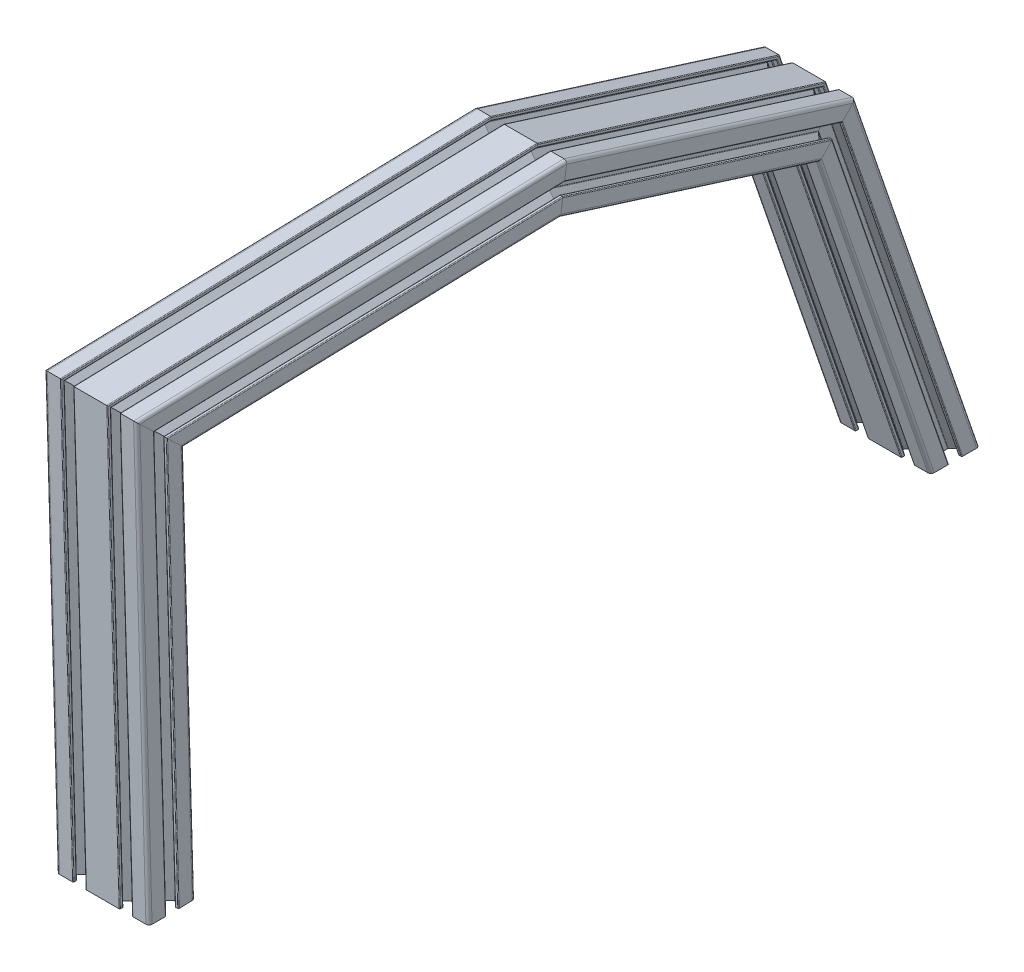
SolidWorks part; units mm, degrees
ref_plane "Front Plane" through (0, 0, 0) normal (0, 0, 1) x (1, 0, 0)
ref_plane "Top Plane" through (0, 0, 0) normal (0, 1, 0) x (1, 0, 0)
ref_plane "Right Plane" through (0, 0, 0) normal (1, 0, 0) x (0, 0, -1)
sketch "Sketch2" plane through (66.7101, 0, 48.5855) normal (0, 1, 0) x (1, 0, 0)
  line L1 (-190.5, -254) -> (190.5, -254)
  line L2 (-190.5, -254) -> (-190.5, 254)
  line L3 (-190.5, 254) -> (190.5, 254)
  line L4 (190.5, -254) -> (190.5, 254)
  line L5 (-190.5, -254) -> (190.5, 254) construction
  line L6 (-190.5, 254) -> (190.5, -254) construction
  point P0 (0, 0)
sketch "Sketch3" plane through (0, 0, 0) normal (0, 1, 0) x (1, 0, 0)
  line L0 (66.7101, -48.5855) -> (66.7101, -302.5855) construction
  line L1 (66.7101, -302.5855) -> (66.7101, 205.4145) construction
  line L2 (-123.7899, -302.5855) -> (257.2101, -302.5855) construction
  line L10 (-123.7899, 205.4145) -> (257.2101, 205.4145) construction
ref_plane "Plane1" through (66.7101, 0, 0) normal (1, 0, 0) x (0, 0, -1)
sketch "Sketch5" plane through (66.7101, 0, 0) normal (1, 0, 0) x (0, 0, -1)
  line L0 (-48.5855, 0) -> (-48.5855, 279.4) construction
  line L1 (-302.5855, 0) -> (-310.1662, 272.1127)
  line L2 (-302.5855, 0) -> (205.4145, 0) construction
  line L3 (-302.5855, 0) -> (205.4145, 0) construction
  line L4 (-310.1662, 272.1127) -> (-48.5855, 279.4)
  line L5 (-48.5855, 279.4) -> (128.7709, 223.4967)
  line L6 (128.7709, 223.4967) -> (217.8615, -36.2959)
  point P28 (217.8615, -36.2959)
  dimension "D1" = 279.4
other "8020 6030(1)" corner treatment miter
ref_plane "Plane2" through (66.7101, 0, 302.5855) normal (0, -0.9996, -0.0278) x (1, 0, 0)
sketch "Sketch21" plane through (66.7101, 0, 302.5855) normal (0, -0.9996, -0.0278) x (1, 0, 0)
  line L0 (11.1749, 2.3185) -> (11.9567, 1.3394) construction
  line L1 (13.6606, 3.0433) -> (12.6815, 3.8251) construction
  line L2 (-4.55, 12.3) -> (-4.55, 9.2682)
  line L3 (4.05, 12.8) -> (-4.05, 12.8)
  line L4 (4.55, 9.2682) -> (4.55, 12.3)
  line L5 (9.0188, 4.178) -> (4.9893, 8.2075)
  line L6 (9.1653, 0.8875) -> (9.1653, 3.8245)
  line L7 (9.6753, -0.0625) -> (9.1653, 0.8875) construction
  line L8 (9.1653, -1.0125) -> (9.6753, -0.0625) construction
  line L9 (9.1653, -3.8245) -> (9.1653, -1.0125)
  line L10 (4.9893, -8.2075) -> (9.0188, -4.178)
  line L11 (4.55, -12.3) -> (4.55, -9.2682)
  line L12 (-4.05, -12.8) -> (4.05, -12.8)
  line L13 (-4.55, -9.2682) -> (-4.55, -12.3)
  line L14 (-9.0188, -4.178) -> (-4.9893, -8.2075)
  line L15 (-9.1653, -1.0125) -> (-9.1653, -3.8245)
  line L16 (-9.6753, -0.0625) -> (-9.1653, -1.0125) construction
  line L17 (-9.1653, 0.8875) -> (-9.6753, -0.0625) construction
  line L18 (-9.1653, 3.8245) -> (-9.1653, 0.8875)
  line L19 (-4.9893, 8.2075) -> (-9.0188, 4.178)
  line L20 (17.3185, 3.8251) -> (16.3393, 3.0433) construction
  line L21 (18.0433, 1.3394) -> (18.8251, 2.3185) construction
  line L22 (18.8251, -2.3185) -> (18.0433, -1.3394) construction
  line L23 (16.3393, -3.0433) -> (17.3185, -3.8251) construction
  line L24 (12.6856, -3.8343) -> (13.6707, -3.0477) construction
  line L25 (11.9608, -1.3486) -> (11.179, -2.3278) construction
  line L26 (-18.8251, 2.3185) -> (-18.0433, 1.3394) construction
  line L27 (-16.3393, 3.0433) -> (-17.3185, 3.8251) construction
  line L28 (-12.6815, 3.8251) -> (-13.6606, 3.0433) construction
  line L29 (-11.9567, 1.3394) -> (-11.1749, 2.3185) construction
  line L30 (-11.1749, -2.3185) -> (-11.9567, -1.3394) construction
  line L31 (-13.6606, -3.0433) -> (-12.6815, -3.8251) construction
  line L32 (-17.3144, -3.8343) -> (-16.3292, -3.0477) construction
  line L33 (-18.0392, -1.3486) -> (-18.821, -2.3278) construction
  line L34 (-24.5, 9.88) -> (-24.5, 13.319)
  line L35 (-28.3189, 9.5) -> (-24.88, 9.5)
  line L36 (-28.6999, 12.7) -> (-28.6999, 9.881)
  line L37 (-24.881, 13.7) -> (-27.6999, 13.7)
  line L38 (-7.2674, -12.7425) -> (-10.4375, -12.7425)
  line L39 (-10.9375, -13.2425) -> (-10.9375, -14.5)
  line L40 (-10.4375, -15) -> (10.4375, -15)
  line L41 (10.9375, -14.5) -> (10.9375, -13.2425)
  line L42 (10.4375, -12.7425) -> (7.2674, -12.7425)
  line L43 (6.75, -12.2428) -> (6.75, -10.2602)
  line L44 (6.8964, -9.9067) -> (10.822, -5.9811)
  line L45 (11.1755, -5.8347) -> (14.05, -5.8347)
  line L46 (14.05, -5.8347) -> (15, -5.3247) construction
  line L47 (15, -5.3247) -> (15.95, -5.8347) construction
  line L48 (15.95, -5.8347) -> (18.8244, -5.8347)
  line L49 (19.178, -5.9811) -> (23.1035, -9.9067)
  line L50 (23.25, -10.2602) -> (23.25, -12.2428)
  line L51 (22.7325, -12.7425) -> (19.4375, -12.7425)
  line L52 (18.9375, -13.2425) -> (18.9375, -14.5)
  line L53 (19.4375, -15) -> (27.9999, -15)
  line L54 (29.9999, -13) -> (29.9999, -4.5625)
  line L55 (29.4999, -4.0625) -> (28.2425, -4.0625)
  line L56 (27.7425, -4.5625) -> (27.7425, -7.7325)
  line L57 (27.2428, -8.25) -> (25.2602, -8.25)
  line L58 (24.9066, -8.1035) -> (20.9811, -4.178)
  line L59 (20.8347, -3.8245) -> (20.8347, -1.0125)
  line L60 (20.8347, -1.0125) -> (20.3247, -0.0625) construction
  line L61 (20.3247, -0.0625) -> (20.8347, 0.8875) construction
  line L62 (20.8347, 0.8875) -> (20.8347, 3.8245)
  line L63 (20.9811, 4.178) -> (24.9066, 8.1035)
  line L64 (25.2602, 8.25) -> (27.2428, 8.25)
  line L65 (27.7425, 7.7325) -> (27.7425, 4.4375)
  line L66 (28.2425, 3.9375) -> (29.4999, 3.9375)
  line L67 (29.9999, 4.4375) -> (29.9999, 13)
  line L68 (27.9999, 15) -> (19.5625, 15)
  line L69 (19.0625, 14.5) -> (19.0625, 13.2425)
  line L70 (19.5625, 12.7425) -> (22.7325, 12.7425)
  line L71 (23.25, 12.2428) -> (23.25, 10.2602)
  line L72 (23.1035, 9.9067) -> (19.178, 5.9811)
  line L73 (18.8244, 5.8347) -> (15.95, 5.8347)
  line L74 (15.95, 5.8347) -> (15, 5.3247) construction
  line L75 (15, 5.3247) -> (14.05, 5.8347) construction
  line L76 (14.05, 5.8347) -> (11.1755, 5.8347)
  line L77 (10.822, 5.9811) -> (6.8964, 9.9067)
  line L78 (6.75, 10.2602) -> (6.75, 12.2428)
  line L79 (7.2674, 12.7425) -> (10.5625, 12.7425)
  line L80 (11.0625, 13.2425) -> (11.0625, 14.5)
  line L81 (10.5625, 15) -> (-10.5625, 15)
  line L82 (-11.0625, 14.5) -> (-11.0625, 13.2425)
  line L83 (-10.5625, 12.7425) -> (-7.2674, 12.7425)
  line L84 (-6.75, 12.2428) -> (-6.75, 10.2602)
  line L85 (-6.8964, 9.9067) -> (-10.822, 5.9811)
  line L86 (-11.1755, 5.8347) -> (-14.05, 5.8347)
  line L87 (-14.05, 5.8347) -> (-15, 5.3247) construction
  line L88 (-15, 5.3247) -> (-15.95, 5.8347) construction
  line L89 (-15.95, 5.8347) -> (-18.8244, 5.8347)
  line L90 (-19.178, 5.9811) -> (-23.1035, 9.9067)
  line L91 (-23.25, 10.2602) -> (-23.25, 12.2428)
  line L92 (-22.7325, 12.7425) -> (-19.5625, 12.7425)
  line L93 (-19.0625, 13.2425) -> (-19.0625, 14.5)
  line L94 (-19.5625, 15) -> (-27.9999, 15)
  line L95 (-29.9999, 13) -> (-29.9999, 4.4375)
  line L96 (-29.4999, 3.9375) -> (-28.2425, 3.9375)
  line L97 (-27.7425, 4.4375) -> (-27.7425, 7.7325)
  line L98 (-27.2428, 8.25) -> (-25.2602, 8.25)
  line L99 (-24.9066, 8.1035) -> (-20.9811, 4.178)
  line L100 (-20.8347, 3.8245) -> (-20.8347, 0.8875)
  line L101 (-20.8347, 0.8875) -> (-20.3247, -0.0625) construction
  line L102 (-20.3247, -0.0625) -> (-20.8347, -1.0125) construction
  line L103 (-20.8347, -1.0125) -> (-20.8347, -3.8245)
  line L104 (-20.9811, -4.178) -> (-24.9066, -8.1035)
  line L105 (-25.2602, -8.25) -> (-27.2428, -8.25)
  line L106 (-27.7425, -7.7325) -> (-27.7425, -4.5625)
  line L107 (-28.2425, -4.0625) -> (-29.4999, -4.0625)
  line L108 (-29.9999, -4.5625) -> (-29.9999, -13)
  line L109 (-27.9999, -15) -> (-19.4375, -15)
  line L110 (-18.9375, -14.5) -> (-18.9375, -13.2425)
  line L111 (-19.4375, -12.7425) -> (-22.7325, -12.7425)
  line L112 (-23.25, -12.2428) -> (-23.25, -10.2602)
  line L113 (-23.1035, -9.9067) -> (-19.178, -5.9811)
  line L114 (-18.8244, -5.8347) -> (-15.95, -5.8347)
  line L115 (-15.95, -5.8347) -> (-15, -5.3247) construction
  line L116 (-15, -5.3247) -> (-14.05, -5.8347) construction
  line L117 (-14.05, -5.8347) -> (-11.1755, -5.8347)
  line L118 (-10.822, -5.9811) -> (-6.8964, -9.9067)
  line L119 (-6.75, -10.2602) -> (-6.75, -12.2428)
  line L120 (-24.88, -9.5) -> (-28.3189, -9.5)
  line L121 (-24.5, -13.319) -> (-24.5, -9.88)
  line L122 (-27.6999, -13.7) -> (-24.881, -13.7)
  line L123 (-28.6999, -9.881) -> (-28.6999, -12.7)
  line L124 (24.5, -9.88) -> (24.5, -13.319)
  line L125 (28.3189, -9.5) -> (24.88, -9.5)
  line L126 (28.6999, -12.7) -> (28.6999, -9.881)
  line L127 (24.881, -13.7) -> (27.6999, -13.7)
  line L128 (27.6999, 13.7) -> (24.881, 13.7)
  line L129 (28.6999, 9.881) -> (28.6999, 12.7)
  line L130 (24.88, 9.5) -> (28.3189, 9.5)
  line L131 (24.5, 13.319) -> (24.5, 9.88)
  line L132 (-14.05, 5.8347) -> (-15.95, 5.8347)
  line L133 (-20.8347, 0.8875) -> (-20.8347, -1.0125)
  line L134 (-15.95, -5.8347) -> (-14.05, -5.8347)
  line L135 (-9.1653, -1.0125) -> (-9.1653, 0.8875)
  line L136 (9.1653, 0.8875) -> (9.1653, -1.0125)
  line L137 (14.05, -5.8347) -> (15.95, -5.8347)
  line L138 (20.8347, -1.0125) -> (20.8347, 0.8875)
  line L139 (15.95, 5.8347) -> (14.05, 5.8347)
  arc A0 (-4.05, 12.8) -> (-4.55, 12.3) centre (-4.05, 12.3) ccw
  arc A1 (4.55, 12.3) -> (4.05, 12.8) centre (4.05, 12.3) ccw
  arc A2 (4.55, 9.2682) -> (4.9893, 8.2075) centre (6.05, 9.2682) ccw
  arc A3 (9.1653, 3.8245) -> (9.0188, 4.178) centre (8.6653, 3.8245) ccw
  arc A4 (9.0188, -4.178) -> (9.1653, -3.8245) centre (8.6653, -3.8245) ccw
  arc A5 (4.9893, -8.2075) -> (4.55, -9.2682) centre (6.05, -9.2682) ccw
  arc A6 (4.05, -12.8) -> (4.55, -12.3) centre (4.05, -12.3) ccw
  arc A7 (-4.55, -12.3) -> (-4.05, -12.8) centre (-4.05, -12.3) ccw
  arc A8 (-4.55, -9.2682) -> (-4.9893, -8.2075) centre (-6.05, -9.2682) ccw
  arc A9 (-9.1653, -3.8245) -> (-9.0188, -4.178) centre (-8.6653, -3.8245) ccw
  arc A10 (-9.0188, 4.178) -> (-9.1653, 3.8245) centre (-8.6653, 3.8245) ccw
  arc A11 (-4.9893, 8.2075) -> (-4.55, 9.2682) centre (-6.05, 9.2682) ccw
  arc A12 (12.6815, 3.8251) -> (11.1749, 2.3185) centre (12.0126, 2.9874) ccw construction
  arc A13 (16.3393, 3.0433) -> (13.6606, 3.0433) centre (15, 0) ccw construction
  arc A14 (18.8251, 2.3185) -> (17.3185, 3.8251) centre (17.9873, 2.9874) ccw construction
  arc A15 (18.0433, -1.3394) -> (18.0433, 1.3394) centre (15, 0) ccw construction
  arc A16 (17.3185, -3.8251) -> (18.8251, -2.3185) centre (17.9873, -2.9874) ccw construction
  arc A17 (13.6707, -3.0477) -> (16.3393, -3.0433) centre (15, 0) ccw construction
  arc A18 (11.179, -2.3278) -> (12.6856, -3.8343) centre (12.0167, -2.9966) ccw construction
  arc A19 (11.9567, 1.3394) -> (11.9608, -1.3486) centre (15, 0) ccw construction
  arc A20 (-17.3185, 3.8251) -> (-18.8251, 2.3185) centre (-17.9873, 2.9874) ccw construction
  arc A21 (-13.6606, 3.0433) -> (-16.3393, 3.0433) centre (-15, 0) ccw construction
  arc A22 (-11.1749, 2.3185) -> (-12.6815, 3.8251) centre (-12.0126, 2.9874) ccw construction
  arc A23 (-11.9567, -1.3394) -> (-11.9567, 1.3394) centre (-15, 0) ccw construction
  arc A24 (-12.6815, -3.8251) -> (-11.1749, -2.3185) centre (-12.0126, -2.9874) ccw construction
  arc A25 (-16.3292, -3.0477) -> (-13.6606, -3.0433) centre (-15, 0) ccw construction
  arc A26 (-18.821, -2.3278) -> (-17.3144, -3.8343) centre (-17.9833, -2.9966) ccw construction
  arc A27 (-18.0433, 1.3394) -> (-18.0392, -1.3486) centre (-15, 0) ccw construction
  arc A28 (-7.2674, -12.7425) -> (-6.75, -12.2428) centre (-7.25, -12.2428) ccw
  arc A29 (-10.4375, -12.7425) -> (-10.9375, -13.2425) centre (-10.4375, -13.2425) ccw
  arc A30 (-10.9375, -14.5) -> (-10.4375, -15) centre (-10.4375, -14.5) ccw
  arc A31 (10.4375, -15) -> (10.9375, -14.5) centre (10.4375, -14.5) ccw
  arc A32 (10.9375, -13.2425) -> (10.4375, -12.7425) centre (10.4375, -13.2425) ccw
  arc A33 (6.75, -12.2428) -> (7.2674, -12.7425) centre (7.25, -12.2428) ccw
  arc A34 (6.8964, -9.9067) -> (6.75, -10.2602) centre (7.25, -10.2602) ccw
  arc A35 (11.1755, -5.8347) -> (10.822, -5.9811) centre (11.1755, -6.3347) ccw
  arc A36 (19.178, -5.9811) -> (18.8244, -5.8347) centre (18.8244, -6.3347) ccw
  arc A37 (23.25, -10.2602) -> (23.1035, -9.9067) centre (22.75, -10.2602) ccw
  arc A38 (22.7325, -12.7425) -> (23.25, -12.2428) centre (22.75, -12.2428) ccw
  arc A39 (19.4375, -12.7425) -> (18.9375, -13.2425) centre (19.4375, -13.2425) ccw
  arc A40 (18.9375, -14.5) -> (19.4375, -15) centre (19.4375, -14.5) ccw
  arc A41 (27.9999, -15) -> (29.9999, -13) centre (27.9999, -13) ccw
  arc A42 (29.9999, -4.5625) -> (29.4999, -4.0625) centre (29.4999, -4.5625) ccw
  arc A43 (28.2425, -4.0625) -> (27.7425, -4.5625) centre (28.2425, -4.5625) ccw
  arc A44 (27.2428, -8.25) -> (27.7425, -7.7325) centre (27.2428, -7.75) ccw
  arc A45 (24.9066, -8.1035) -> (25.2602, -8.25) centre (25.2602, -7.75) ccw
  arc A46 (20.8347, -3.8245) -> (20.9811, -4.178) centre (21.3347, -3.8245) ccw
  arc A47 (20.9811, 4.178) -> (20.8347, 3.8245) centre (21.3347, 3.8245) ccw
  arc A48 (25.2602, 8.25) -> (24.9066, 8.1035) centre (25.2602, 7.75) ccw
  arc A49 (27.7425, 7.7325) -> (27.2428, 8.25) centre (27.2428, 7.75) ccw
  arc A50 (27.7425, 4.4375) -> (28.2425, 3.9375) centre (28.2425, 4.4375) ccw
  arc A51 (29.4999, 3.9375) -> (29.9999, 4.4375) centre (29.4999, 4.4375) ccw
  arc A52 (29.9999, 13) -> (27.9999, 15) centre (27.9999, 13) ccw
  arc A53 (19.5625, 15) -> (19.0625, 14.5) centre (19.5625, 14.5) ccw
  arc A54 (19.0625, 13.2425) -> (19.5625, 12.7425) centre (19.5625, 13.2425) ccw
  arc A55 (23.25, 12.2428) -> (22.7325, 12.7425) centre (22.75, 12.2428) ccw
  arc A56 (23.1035, 9.9067) -> (23.25, 10.2602) centre (22.75, 10.2602) ccw
  arc A57 (18.8244, 5.8347) -> (19.178, 5.9811) centre (18.8244, 6.3347) ccw
  arc A58 (10.822, 5.9811) -> (11.1755, 5.8347) centre (11.1755, 6.3347) ccw
  arc A59 (6.75, 10.2602) -> (6.8964, 9.9067) centre (7.25, 10.2602) ccw
  arc A60 (7.2674, 12.7425) -> (6.75, 12.2428) centre (7.25, 12.2428) ccw
  arc A61 (10.5625, 12.7425) -> (11.0625, 13.2425) centre (10.5625, 13.2425) ccw
  arc A62 (11.0625, 14.5) -> (10.5625, 15) centre (10.5625, 14.5) ccw
  arc A63 (-10.5625, 15) -> (-11.0625, 14.5) centre (-10.5625, 14.5) ccw
  arc A64 (-11.0625, 13.2425) -> (-10.5625, 12.7425) centre (-10.5625, 13.2425) ccw
  arc A65 (-6.75, 12.2428) -> (-7.2674, 12.7425) centre (-7.25, 12.2428) ccw
  arc A66 (-6.8964, 9.9067) -> (-6.75, 10.2602) centre (-7.25, 10.2602) ccw
  arc A67 (-11.1755, 5.8347) -> (-10.822, 5.9811) centre (-11.1755, 6.3347) ccw
  arc A68 (-19.178, 5.9811) -> (-18.8244, 5.8347) centre (-18.8244, 6.3347) ccw
  arc A69 (-23.25, 10.2602) -> (-23.1035, 9.9067) centre (-22.75, 10.2602) ccw
  arc A70 (-22.7325, 12.7425) -> (-23.25, 12.2428) centre (-22.75, 12.2428) ccw
  arc A71 (-19.5625, 12.7425) -> (-19.0625, 13.2425) centre (-19.5625, 13.2425) ccw
  arc A72 (-19.0625, 14.5) -> (-19.5625, 15) centre (-19.5625, 14.5) ccw
  arc A73 (-27.9999, 15) -> (-29.9999, 13) centre (-27.9999, 13) ccw
  arc A74 (-29.9999, 4.4375) -> (-29.4999, 3.9375) centre (-29.4999, 4.4375) ccw
  arc A75 (-28.2425, 3.9375) -> (-27.7425, 4.4375) centre (-28.2425, 4.4375) ccw
  arc A76 (-27.2428, 8.25) -> (-27.7425, 7.7325) centre (-27.2428, 7.75) ccw
  arc A77 (-24.9066, 8.1035) -> (-25.2602, 8.25) centre (-25.2602, 7.75) ccw
  arc A78 (-20.8347, 3.8245) -> (-20.9811, 4.178) centre (-21.3347, 3.8245) ccw
  arc A79 (-20.9811, -4.178) -> (-20.8347, -3.8245) centre (-21.3347, -3.8245) ccw
  arc A80 (-25.2602, -8.25) -> (-24.9066, -8.1035) centre (-25.2602, -7.75) ccw
  arc A81 (-27.7425, -7.7325) -> (-27.2428, -8.25) centre (-27.2428, -7.75) ccw
  arc A82 (-27.7425, -4.5625) -> (-28.2425, -4.0625) centre (-28.2425, -4.5625) ccw
  arc A83 (-29.4999, -4.0625) -> (-29.9999, -4.5625) centre (-29.4999, -4.5625) ccw
  arc A84 (-29.9999, -13) -> (-27.9999, -15) centre (-27.9999, -13) ccw
  arc A85 (-19.4375, -15) -> (-18.9375, -14.5) centre (-19.4375, -14.5) ccw
  arc A86 (-18.9375, -13.2425) -> (-19.4375, -12.7425) centre (-19.4375, -13.2425) ccw
  arc A87 (-23.25, -12.2428) -> (-22.7325, -12.7425) centre (-22.75, -12.2428) ccw
  arc A88 (-23.1035, -9.9067) -> (-23.25, -10.2602) centre (-22.75, -10.2602) ccw
  arc A89 (-18.8244, -5.8347) -> (-19.178, -5.9811) centre (-18.8244, -6.3347) ccw
  arc A90 (-10.822, -5.9811) -> (-11.1755, -5.8347) centre (-11.1755, -6.3347) ccw
  arc A91 (-6.75, -10.2602) -> (-6.8964, -9.9067) centre (-7.25, -10.2602) ccw
  arc A92 (-24.88, 9.5) -> (-24.5, 9.88) centre (-24.88, 9.88) ccw
  arc A93 (-28.6999, 9.881) -> (-28.3189, 9.5) centre (-28.3189, 9.881) ccw
  arc A94 (-27.6999, 13.7) -> (-28.6999, 12.7) centre (-27.6999, 12.7) ccw
  arc A95 (-24.5, 13.319) -> (-24.881, 13.7) centre (-24.881, 13.319) ccw
  arc A96 (-24.5, -9.88) -> (-24.88, -9.5) centre (-24.88, -9.88) ccw
  arc A97 (-24.881, -13.7) -> (-24.5, -13.319) centre (-24.881, -13.319) ccw
  arc A98 (-28.6999, -12.7) -> (-27.6999, -13.7) centre (-27.6999, -12.7) ccw
  arc A99 (-28.3189, -9.5) -> (-28.6999, -9.881) centre (-28.3189, -9.881) ccw
  arc A100 (24.88, -9.5) -> (24.5, -9.88) centre (24.88, -9.88) ccw
  arc A101 (28.6999, -9.881) -> (28.3189, -9.5) centre (28.3189, -9.881) ccw
  arc A102 (27.6999, -13.7) -> (28.6999, -12.7) centre (27.6999, -12.7) ccw
  arc A103 (24.5, -13.319) -> (24.881, -13.7) centre (24.881, -13.319) ccw
  arc A104 (28.6999, 12.7) -> (27.6999, 13.7) centre (27.6999, 12.7) ccw
  arc A105 (28.3189, 9.5) -> (28.6999, 9.881) centre (28.3189, 9.881) ccw
  arc A106 (24.5, 9.88) -> (24.88, 9.5) centre (24.88, 9.88) ccw
  arc A107 (24.881, 13.7) -> (24.5, 13.319) centre (24.881, 13.319) ccw
  circle A108 centre (-15, 0) radius 3.325
  circle A109 centre (15, 0) radius 3.325
  point P350 (0, 0)
sketch "Sketch22" plane through (0, 0, 0) normal (0, 1, 0) x (1, 0, 0)
  line L1 (-241.4619, 285.031) -> (374.882, 285.031)
  line L2 (-241.4619, 285.031) -> (-241.4619, -382.202)
  line L3 (-241.4619, -382.202) -> (374.882, -382.202)
  line L4 (374.882, 285.031) -> (374.882, -382.202)
  line L5 (-241.4619, 285.031) -> (374.882, -382.202) construction
  line L6 (-241.4619, -382.202) -> (374.882, 285.031) construction
  point P0 (66.7101, -48.5855)
extrude "Cut-Extrude1" cut sketch "Sketch22" against normal through all
